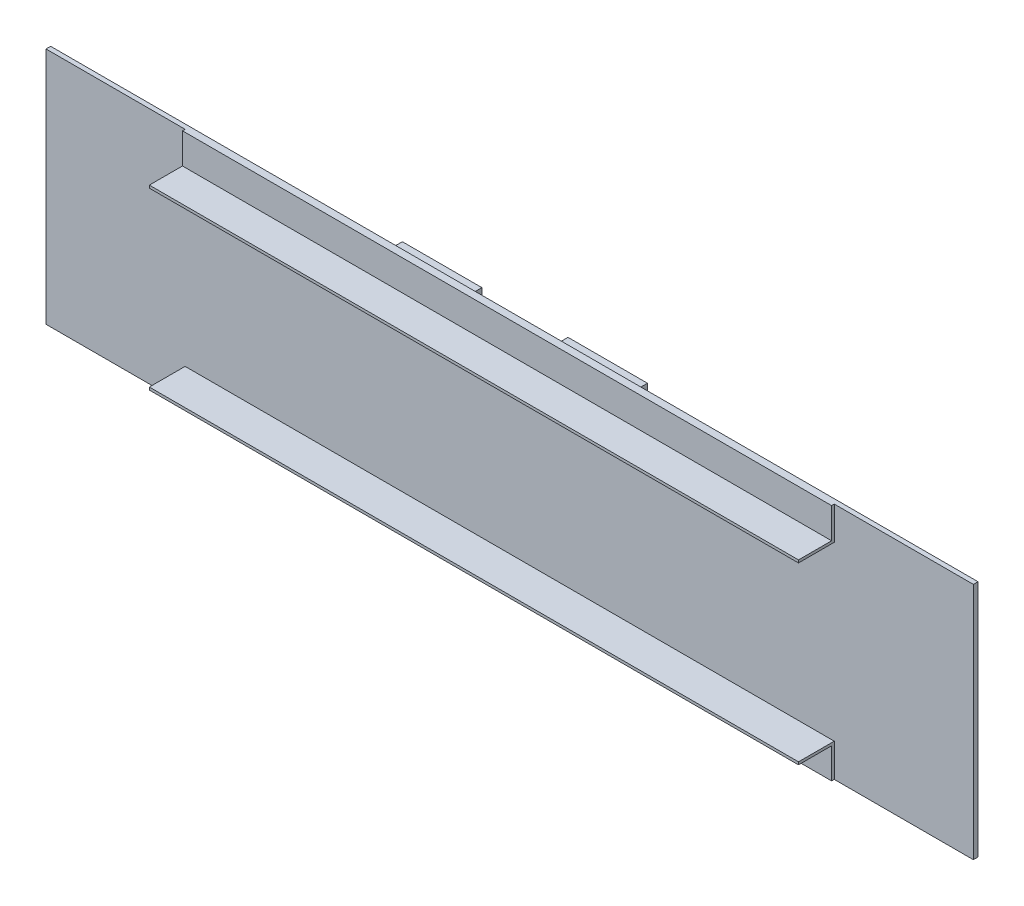
SolidWorks part; units mm, degrees
ref_plane "前视基准面" through (0, 0, 0) normal (0, 0, 1) x (1, 0, 0)
ref_plane "上视基准面" through (0, 0, 0) normal (0, 1, 0) x (1, 0, 0)
ref_plane "右视基准面" through (0, 0, 0) normal (1, 0, 0) x (0, 0, -1)
sketch "草图1" plane through (0, 0, 0) normal (0, 0, 1) x (1, 0, 0)
  line L1 (-1400, 360) -> (1400, 360)
  line L2 (-1400, 360) -> (-1400, -360)
  line L3 (-1400, -360) -> (1400, -360)
  line L4 (1400, 360) -> (1400, -360)
  line L5 (-1400, 360) -> (1400, -360) construction
  line L6 (-1400, -360) -> (1400, 360) construction
  point P0 (0, 0)
extrude "凸台-拉伸1" add sketch "草图1" along normal blind 14
sketch "草图2" plane through (0, 0, 14) normal (0, 0, 1) x (1, 0, 0)
  line L0 (-1400, 300) -> (1400, 300)
  line L1 (-1400, 360) -> (-1400, -360) construction
  line L2 (1400, -360) -> (1400, 360) construction
  line L3 (1400, 360) -> (-1400, 360) construction
  line L4 (-1400, 304) -> (1400, 304)
  line L5 (-1330, 360) -> (-1330, -360)
  line L6 (-1400, -360) -> (1400, -360) construction
  line L7 (-1030, 360) -> (-1030, -360)
  line L8 (-980, 360) -> (-980, -360)
  dimension "D1" = 60
  dimension "D2" = 56
  dimension "D3" = 70
  dimension "D4" = 370
  dimension "D5" = 420
sketch "草图5" plane through (0, 0, 14) normal (0, 0, 1) x (1, 0, 0)
  line L1 (-980, 360) -> (0, 360)
  line L2 (-980, 360) -> (-980, 260)
  line L3 (-980, 260) -> (0, 260)
  line L4 (0, 360) -> (0, 260)
extrude "凸台-拉伸2" add sketch "草图5" along normal blind 8
sketch "草图6" plane through (0, 0, 14) normal (0, 0, 1) x (1, 0, 0)
  line L0 (-930, 360) -> (-930, -360)
  line L1 (0, 360) -> (-980, 360) construction
  line L2 (-1400, -360) -> (1400, -360) construction
  line L3 (-980, 360) -> (-980, -360) construction
  line L4 (-450, 360) -> (-450, -360)
  line L5 (-330, 360) -> (-330, -360)
  line L6 (-50, 360) -> (-50, -360)
  dimension "D1" = 50
  dimension "D2" = 530
  dimension "D3" = 650
  dimension "D4" = 930
sketch "草图9" plane through (0, 0, 22) normal (0, 0, 1) x (1, 0, 0)
  line L0 (0, 260) -> (0, 360) construction
  line L1 (-980, 260) -> (0, 260)
  line L2 (-980, 260) -> (-980, 268)
  line L3 (-980, 268) -> (0, 268)
  line L4 (0, 260) -> (0, 268)
extrude "凸台-拉伸3" add sketch "草图9" along normal blind 100
mirror "镜向3" about plane through (0, 0, 0) normal (0, 1, 0) of "凸台-拉伸2", "凸台-拉伸3"
mirror "镜向4" about plane through (0, 0, 0) normal (1, 0, 0) of "镜向3"
sketch "草图10" plane through (0, 0, 0) normal (0, 0, -1) x (-1, 0, 0)
  line L0 (370, -360) -> (370, 360)
  line L1 (1400, -360) -> (-1400, -360) construction
  line L2 (-1400, 360) -> (1400, 360) construction
  line L3 (330, 360) -> (330, -360) construction
  dimension "D1" = 40
sketch "草图11" plane through (0, 0, 22) normal (0, 0, 1) x (1, 0, 0)
  line L0 (-370, -360) -> (-370, 360) construction
  line L1 (-370, 268) -> (-130, 268)
  line L2 (-370, 268) -> (-370, 348)
  line L3 (-370, 348) -> (-130, 348)
  line L4 (-130, 268) -> (-130, 348)
  line L5 (980, 268) -> (-980, 268) construction
extrude "凸台-拉伸4" add sketch "草图11" against normal blind 32
sketch "草图12" plane through (0, 0, 22) normal (0, 0, 1) x (1, 0, 0)
  line L0 (-1400, 304) -> (1400, 304) construction
  line L1 (-330, 360) -> (-330, -360) construction
  circle A0 centre (-330, 304) radius 13
extrude "切除-拉伸5" cut sketch "草图12" against normal through all
pattern_linear "阵列(线性)4" count 3 spacing 80 along (1, 0, 0) of "切除-拉伸5"
extrude "凸台-拉伸6" add sketch "草图11<3>" against normal blind 54
sketch "草图11<3>" plane through (0, 0, 22) normal (0, 0, 1) x (1, 0, 0) same geometry as "草图11"
mirror "镜向7" about plane through (0, 0, 0) normal (0, 1, 0) of "凸台-拉伸6"
mirror "镜向8" about plane through (0, 0, 0) normal (1, 0, 0) of "镜向7"
